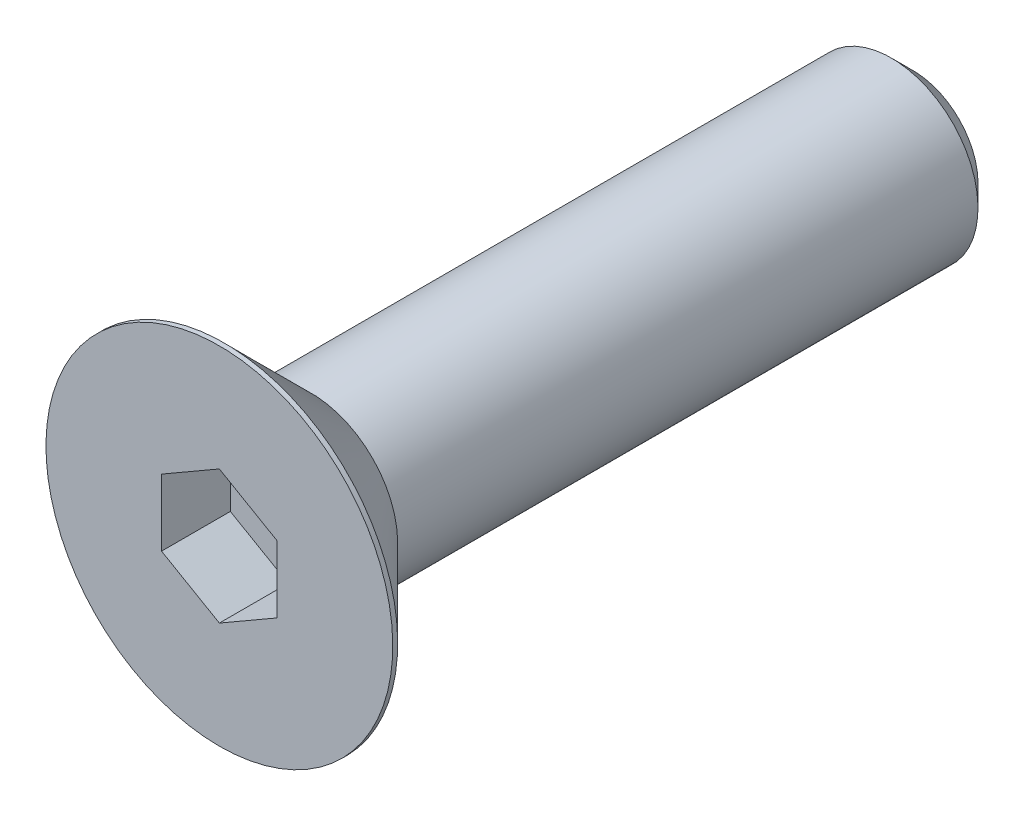
SolidWorks part; units mm, degrees
material "Chrome Stainless Steel"
ref_plane "Front" through (0, 0, 0) normal (0, 0, 1) x (1, 0, 0)
ref_plane "Top" through (0, 0, 0) normal (0, 1, 0) x (1, 0, 0)
ref_plane "Right" through (0, 0, 0) normal (1, 0, 0) x (0, 0, -1)
sketch "Sketch11" plane through (0, 0, 0) normal (1, 0, 0) x (0, 0, -1)
  line L0 (-6, 3) -> (6, 3) construction
  line L5 (-6, 3) -> (-6, -3) construction
  line L6 (6, 1.5) -> (6, -1.5) construction
  line L7 (-5.99, 1) -> (-5.99, -1) construction
  line L8 (5.9688, 1.5541) -> (6.4688, 1.5541) construction
  line L9 (6.4688, 1.5541) -> (6.2188, 1.1211) construction
  line L10 (6.2188, 1.1211) -> (5.9688, 1.5541) construction
  line L11 (6.1875, 1.1752) -> (6.25, 1.1752) construction
  line L12 (6.2188, 1.1752) -> (6.2188, 1.1211) construction
  line L13 (5.9844, 1.5271) -> (6.4531, 1.5271) construction
  line L14 (6.2188, 1.5541) -> (6.2188, 1.5) construction
  line L15 (6, 1.5) -> (6.4375, 1.5) construction
  line L17 (-5.915, 3) -> (-2.915, 0) construction
  line L18 (-2.915, 0) -> (-5.915, -3) construction
  point P3 (-4.3, 3)
  point P8 (0, 3)
  point P21 (6.2188, 1.5271)
  point P26 (-6, 0)
  point P28 (-5.99, 0)
  point P29 (6, 0)
  dimension "Length" = 12
  dimension "Head Diameter" = 6
  dimension "Thread Major Diameter" = 3
  dimension "Head Height" = 1.7
  dimension "Drive Size" = 2
  dimension "Thread Pitch" = 0.5
  dimension "D1" = 0.0625
  dimension "D2" = 0.01
  dimension "D3" = 0.085
  dimension "Countersink Angle" = 90
sketch "Sketch1" plane through (0, 0, 0) normal (1, 0, 0) x (0, 0, -1)
  line L2 (-4.3, 1.5) -> (6, 1.5)
  line L3 (6, 1.5) -> (6, 0)
  line L4 (-4.81, 1.5) -> (-4.81, 0)
  line L5 (-4.3, 1.5) -> (-4.81, 1.5)
  line L6 (-6, 3) -> (-6, -3) construction
  line L7 (6, 1.5) -> (6, -1.5) construction
  line L8 (-4.81, 0) -> (6, 0)
  dimension "D1" = 1.19
revolve "Revolve1" add sketch "Sketch1" angle 360 mid plane about L8
chamfer "Chamfer1" distance 0.375 angle 45 1 edges at (0, -1.5, -6)
sketch "Sketch7" plane through (0, 0, 0) normal (1, 0, 0) x (0, 0, -1)
  line L2 (-6, 3) -> (-5.915, 3)
  line L5 (-4.3, 1.385) -> (-4.3, 0)
  line L6 (-6, 3) -> (-6, 0)
  line L8 (-6, 3) -> (-6, -3) construction
  line L9 (-6, 0) -> (-4.3, 0)
  line L12 (-5.915, 3) -> (-4.3, 1.385)
  line L13 (-5.915, 3) -> (-2.915, 0) construction
revolve "Revolve2" add sketch "Sketch7" angle 360 mid plane about L9 region at (0, 1.1696, 5.2571)
ref_plane "Plane1" through (0, 0, 4.3) normal (0, 0, 1) x (1, 0, 0)
sketch "Sketch5" plane through (0, 0, 6) normal (0, 0, 1) x (1, 0, 0)
  line L1 (1, -0.5774) -> (1, 0.5774)
  line L2 (1, 0.5774) -> (0, 1.1547)
  line L3 (0, 1.1547) -> (-1, 0.5774)
  line L4 (-1, 0.5774) -> (-1, -0.5774)
  line L5 (-1, -0.5774) -> (0, -1.1547)
  line L6 (0, -1.1547) -> (1, -0.5774)
  circle A0 centre (0, 0) radius 1 construction
extrude "Cut-Extrude2" cut sketch "Sketch5" against normal blind 1.19
sketch "Sketch6" plane through (0, 0, 6) normal (0, 0, -1) x (-1, 0, 0)
  circle A0 centre (0, 0) radius 1.1547
extrude "Cut-Extrude3" [suppressed] cut sketch "Sketch6" along normal blind 1.19 draft 45
sketch "Sketch12" [suppressed] plane through (0, 0, -6) normal (0, 0, -1) x (-1, 0, 0)
  circle A0 centre (0, 0) radius 1.5 construction
  circle A1 centre (0, 0) radius 1.5
curve "Helix/Spiral1" [suppressed] pitch 0.5 height 12 turns 24
sketch "Sketch13" [suppressed] plane through (0, 0, 0) normal (1, 0, 0) x (0, 0, -1)
  line L0 (5.9844, 1.5271) -> (6.4531, 1.5271)
  line L1 (6.4531, 1.5271) -> (6.25, 1.1752)
  line L2 (6.25, 1.1752) -> (6.1875, 1.1752)
  line L3 (6.1875, 1.1752) -> (5.9844, 1.5271)
sweep "Cut-Sweep1" [suppressed] cut profiles "Sketch13" path "Helix/Spiral1"
combine bodies "Combine1" [suppressed] operation type add bodies to combine 113 127
equation "\"D1@Chamfer1\"=\"Thread Pitch@Sketch11\" * .75"
equation "\"D1@Cut-Extrude2\"= \"Head Height@Sketch11\" * .7"
equation "\"D1@Cut-Extrude3\" = \"D1@Cut-Extrude2\""
equation "\"D1@Sketch11\"=\"Thread Pitch@Sketch11\"/8"
equation "\"D3@Sketch11\"=\"Head Height@Sketch11\"*.05"
equation "\"D4@Helix/Spiral1\"=\"Thread Pitch@Sketch11\""
equation "\"D1@Sketch1\"=\"Head Height@Sketch11\"*.7"
equation "\"D3@Helix/Spiral1\"=\"Length@Sketch11\""
